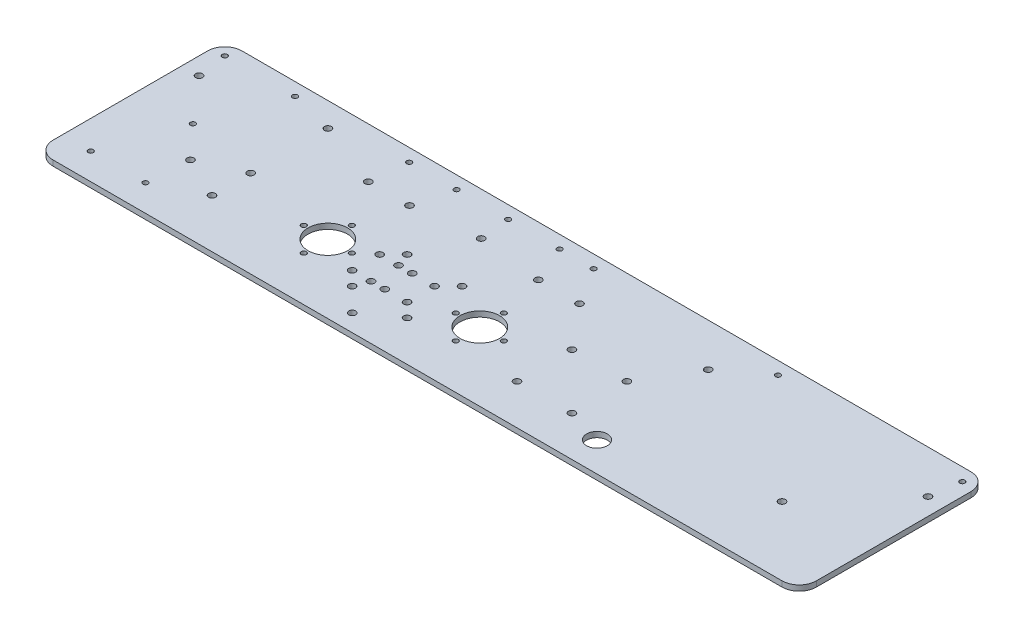
SolidWorks part; units mm, degrees
ref_plane "Front" through (0, 0, 0) normal (0, 0, 1) x (1, 0, 0)
ref_plane "Top" through (0, 0, 0) normal (0, 1, 0) x (1, 0, 0)
ref_plane "Right" through (0, 0, 0) normal (1, 0, 0) x (0, 0, -1)
sketch "Sketch1" plane through (0, 0, 0) normal (0, 1, 0) x (1, 0, 0)
  line L0 (-26.7996, 0) -> (-26.7996, 40)
  line L1 (-26.7996, 0) -> (417.7004, 0)
  line L2 (-26.7996, 0) -> (-26.7996, 110)
  line L3 (-26.7996, 110) -> (417.7004, 110)
  line L4 (417.7004, 0) -> (417.7004, 110)
  line L5 (-26.7996, 40) -> (23.2004, 40)
  line L6 (417.7004, 0) -> (417.7004, 40)
  line L7 (417.7004, 40) -> (367.7004, 40)
  line L8 (23.2004, 40) -> (103.2004, 40)
  line L9 (367.7004, 40) -> (191.7004, 40)
  line L10 (-26.7996, 110) -> (-26.7996, 85)
  line L11 (-26.7996, 85) -> (417.7004, 85)
  line L12 (-26.7996, 85) -> (-16.7996, 85)
  line L13 (417.7004, 85) -> (407.7004, 85)
  line L14 (103.2004, 40) -> (191.7004, 40)
  line L15 (147.4504, 40) -> (147.4504, 85)
  line L16 (279.7004, 40) -> (279.7004, 85)
  line L17 (147.4504, 40) -> (147.4504, 10)
  line L18 (-26.7996, 110) -> (-26.7996, 102.5)
  line L19 (-26.7996, 102.5) -> (417.7004, 102.5)
  line L20 (-26.7996, 102.5) -> (-19.2996, 102.5)
  line L21 (417.7004, 102.5) -> (410.2004, 102.5)
  line L22 (195.4504, 102.5) -> (410.2004, 102.5)
  line L23 (-19.2996, 102.5) -> (195.4504, 102.5)
  line L24 (417.7004, 0) -> (417.7004, 17.2282)
  line L25 (417.7004, 17.2282) -> (282.7004, 17.2282)
  circle A10 centre (367.7004, 40) radius 2
  circle A11 centre (23.2004, 40) radius 2
  circle A12 centre (103.2004, 40) radius 11.5
  circle A13 centre (103.2004, 40) radius 14
  circle A15 centre (103.2004, 54) radius 1.5
  circle A16 centre (89.2004, 40) radius 1.5
  circle A17 centre (103.2004, 26) radius 1.5
  circle A18 centre (117.2004, 40) radius 1.5
  circle A19 centre (191.7004, 40) radius 11.5
  circle A20 centre (191.7004, 40) radius 14
  circle A21 centre (191.7004, 26) radius 1.5
  circle A22 centre (205.7004, 40) radius 1.5
  circle A23 centre (191.7004, 54) radius 1.5
  circle A24 centre (177.7004, 40) radius 1.5
  circle A25 centre (-16.7996, 85) radius 2
  circle A26 centre (407.7004, 85) radius 2
  circle A27 centre (147.4504, 85) radius 2
  circle A28 centre (279.7004, 85) radius 2
  circle A29 centre (147.4504, 10) radius 2
  circle A30 centre (195.4504, 102.5) radius 1.5
  circle A31 centre (-19.2996, 102.5) radius 1.5
  circle A32 centre (410.2004, 102.5) radius 1.5
  circle A33 centre (302.8254, 102.5) radius 1.5
  circle A34 centre (88.0754, 102.5) radius 1.5
  circle A35 centre (282.7004, 17.2282) radius 6
  dimension "D3" = 40
  dimension "D7" = 80
  dimension "D8" = 176
  dimension "D9" = 25
  dimension "D11" = 10
  dimension "D12" = 30
  dimension "D13" = 7.5
  dimension "D14" = 7.5
  dimension "D16" = 17.2282
  dimension "D1" = 110
  dimension "D2" = 444.5
  dimension "D4" = 50
  dimension "D5" = 40
  dimension "D6" = 50
  dimension "D10" = 10
  dimension "D15" = 7.5
  dimension "D17" = 135
extrude "Boss-Extrude1" add sketch "Sketch1" along normal blind 3.175 contours A18 L14 A12 L8 A16 A13 A17 | A18 A13 A15 A16 L8 A12 L14 | A24 L14 A19 L9 A22 A20 A23 | A24 A20 A21 A22 L9 A19 L14 | A29 L14 A18 A13 A17 A16 L8 A11 L5 L0 L1 L4 L7 A10 L9 A22 A20 A21 A24 | A28 L11 A27 L15 L14 A24 A20 A23 A22 L9 L16 | A27 L11 A25 L2 L5 A11 L8 A16 A13 A15 A18 L14 L15 | A28 L11 A26 L13 L4 L3 L2 A25 A27 | A28 L16 L9 A10 L7 L4 L13 A26 L11 | A34 L23 A30 L22 A33 A32 L21 L4 L3 L10 L19 A31 region at (196.684, 0, -19.4923) region at (58.5861, 0, -63.184) region at (195.421, 0, -93.7571) region at (195.4504, 0, -106.2666) region at (348.6559, 0, -62.489) region at (93.521, 0, -49.6794) region at (90.515, 0, -38.754) region at (214.7998, 0, -63.4004) region at (204.3858, 0, -41.246) region at (201.3798, 0, -30.3206)
fillet "Fillet1" radius 10 4 edges at (417.7004, 1.5875, -110) (417.7004, 1.5875, 0) (-26.7996, 1.5875, 0) (-26.7996, 1.5875, -110)
sketch "Sketch2" plane through (0, 3.175, 0) normal (0, 1, 0) x (1, 0, 0)
  line L0 (-26.7996, 55.4056) -> (36.2004, 55.4056)
  line L1 (-26.7996, 10) -> (-26.7996, 100) construction
  line L2 (36.2004, 55.4056) -> (76.2004, 55.4056)
  line L3 (-16.7996, 110) -> (407.7004, 110) construction
  line L4 (36.2004, 55.4056) -> (36.2004, 23.4056)
  line L5 (36.2004, 23.4056) -> (68.2004, 23.4056)
  line L6 (76.2004, 55.4056) -> (165.9504, 55.4056)
  line L7 (165.9504, 55.4056) -> (133.9504, 55.4056)
  line L8 (133.9504, 55.4056) -> (133.9504, 23.4056)
  line L9 (133.9504, 23.4056) -> (165.9504, 23.4056)
  line L10 (133.9504, 23.4056) -> (125.9504, 23.4056)
  line L11 (125.9504, 23.4056) -> (125.9504, 55.4056)
  line L12 (165.9504, 55.4056) -> (157.9504, 55.4056)
  line L13 (157.9504, 55.4056) -> (157.9504, 23.4056)
  line L14 (157.9504, 23.4056) -> (157.9504, 31.4056)
  line L15 (157.9504, 55.4056) -> (157.9504, 47.4056)
  line L16 (157.9504, 47.4056) -> (133.9504, 47.4056)
  circle A4 centre (133.9504, 55.4056) radius 2
  circle A5 centre (165.9504, 55.4056) radius 2
  circle A9 centre (133.9504, 23.4056) radius 2
  circle A10 centre (165.9504, 23.4056) radius 2
  circle A11 centre (157.9504, 31.4056) radius 2
  circle A12 centre (125.9504, 31.4056) radius 2
  circle A13 centre (125.9504, 47.4056) radius 2
  circle A14 centre (157.9504, 47.4056) radius 2
  dimension "D5" = 89.75
  dimension "D6" = 32
  dimension "D7" = 8
  dimension "D10" = 8
  dimension "D1" = 63
  dimension "D2" = 40
  dimension "D3" = 54.5944
  dimension "D4" = 32
  dimension "D8" = 8
  dimension "D9" = 8
extrude "Cut-Extrude1" cut sketch "Sketch2" against normal blind 10 contours A4 | A5 | A13 | A12 | A9 | A10 | A11 | A14
sketch "Sketch3" plane through (0, 0, 0) normal (0, -1, 0) x (1, 0, 0)
  line L0 (133.9504, -55.4056) -> (133.9504, -47.4056)
  line L1 (133.9504, -47.4056) -> (136.9504, -47.4056)
  line L2 (136.9504, -47.4056) -> (144.9504, -47.4056)
  line L3 (136.9504, -47.4056) -> (136.9504, -31.4056)
  line L4 (136.9504, -31.4056) -> (144.9504, -31.4056)
  line L5 (165.9504, -55.4056) -> (229.9504, -55.4056)
  line L6 (229.9504, -55.4056) -> (261.9504, -55.4056)
  line L7 (261.9504, -55.4056) -> (261.9504, -23.4056)
  line L8 (261.9504, -23.4056) -> (229.9504, -23.4056)
  circle A0 centre (144.9504, -47.4056) radius 2
  circle A1 centre (136.9504, -47.4056) radius 2
  circle A2 centre (144.9504, -31.4056) radius 2
  circle A3 centre (136.9504, -31.4056) radius 2
  circle A4 centre (261.9504, -55.4056) radius 2
  circle A5 centre (229.9504, -55.4056) radius 2
  circle A6 centre (261.9504, -23.4056) radius 2
  circle A7 centre (229.9504, -23.4056) radius 2
  dimension "D3" = 8
  dimension "D5" = 64
  dimension "D7" = 32
  dimension "D1" = 3
  dimension "D2" = 8
  dimension "D4" = 16
  dimension "D6" = 32
extrude "Cut-Extrude2" cut sketch "Sketch3" against normal blind 10 contours L2 A1 L1 | L1 A1 L2 | A2 | L4 A3 L3 | L3 A1 L1 | L3 A3 L4 | A0 | A4 | A6 | A7 | A5 region at (136.1016, 0, -46.5568) region at (144.9504, 0, -29.4622) region at (136.6675, 0, -31.1227) region at (137.7992, 0, -32.2544) region at (136.9504, 0, -48.2544) region at (137.7992, 0, -46.5568)
sketch "Sketch4" plane through (0, 3.175, 0) normal (0, 1, 0) x (1, 0, 0)
  circle A0 centre (21.5907, 102.5) radius 1.5
  circle A1 centre (5.6648, 58.9528) radius 1.5
  circle A2 centre (-10.261, 15.4056) radius 1.5
  circle A3 centre (47.3504, 50.9056) radius 2
  circle A4 centre (115.6708, 102.5) radius 1.5
  circle A5 centre (145.6708, 102.5) radius 1.5
  circle A6 centre (175.6708, 102.5) radius 1.5
  circle A7 centre (47.3504, 95.9056) radius 2
  circle A8 centre (21.5907, 15.4056) radius 1.5
  circle A9 centre (47.3504, 28.4056) radius 2
  circle A10 centre (208.9504, 80.8056) radius 2
  circle A11 centre (184.9504, 80.8056) radius 2
  circle A12 centre (109.9504, 80.8056) radius 2
  circle A13 centre (85.9504, 80.8056) radius 2
extrude "Cut-Extrude3" cut sketch "Sketch4" against normal blind 6.35
